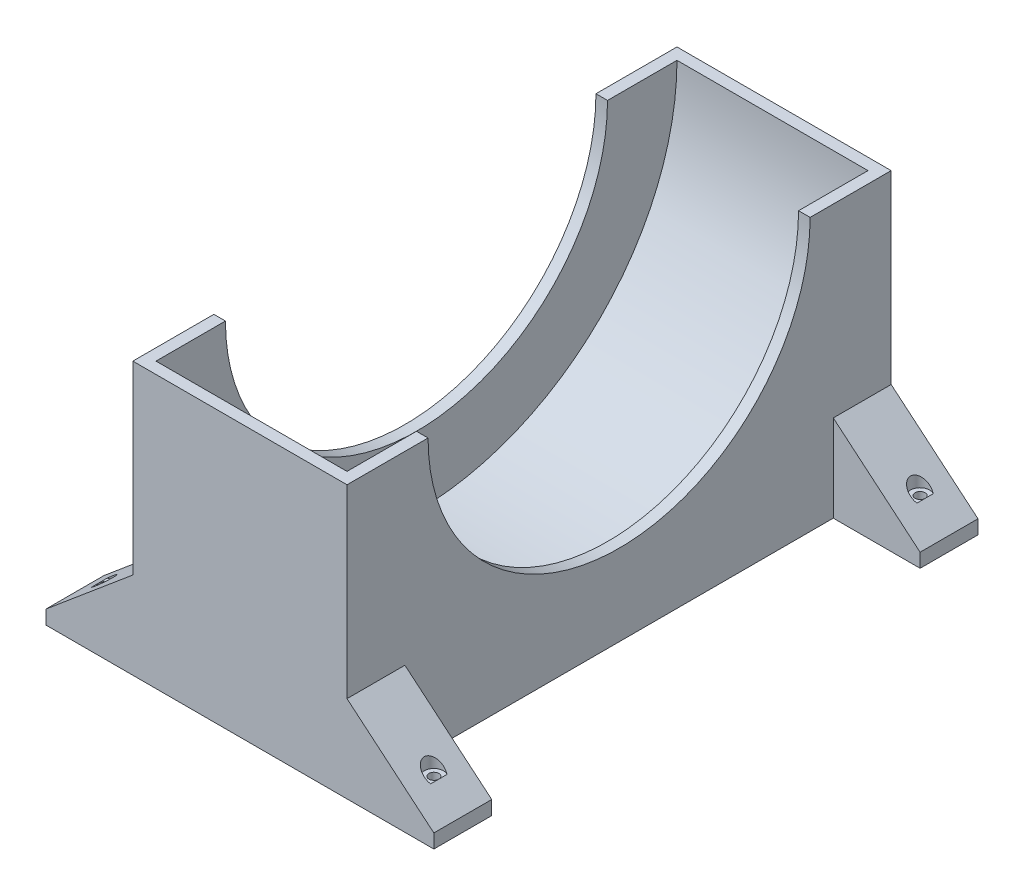
SolidWorks part; units mm, degrees
ref_plane "Front Plane" through (0, 0, 0) normal (0, 0, 1) x (1, 0, 0)
ref_plane "Top Plane" through (0, 0, 0) normal (0, 1, 0) x (1, 0, 0)
ref_plane "Right Plane" through (0, 0, 0) normal (1, 0, 0) x (0, 0, -1)
sketch "Sketch1" plane through (0, 0, 0) normal (1, 0, 0) x (0, 0, -1)
  line L9 (-119.38, 0) -> (-83.82, 0)
  line L10 (83.82, 0) -> (119.38, 0)
  arc A2 (-83.82, 0) -> (83.82, 0) centre (0, 0) ccw
  arc A3 (-119.38, 0) -> (119.38, 0) centre (0, 0) ccw
  dimension "D1" = 83.82
  dimension "D2" = 119.38
extrude "Boss-Extrude1" add sketch "Sketch1" along normal blind 93.98
shell "Shell2" thickness 5.08 removed face at (46.99, 0, -101.6) removed face at (46.99, -41.91, 0) removed face at (46.99, 0, 101.6)
sketch "Sketch6" plane through (0, 0, 0) normal (1, 0, 0) x (0, 0, -1)
  line L3 (-119.38, 0) -> (-119.38, -119.38)
  line L4 (-119.38, -119.38) -> (0, -119.38)
  arc A0 (-119.38, 0) -> (0, -119.38) centre (0, 0) ccw
  dimension "D1" = 119.38
extrude "Boss-Extrude2" add sketch "Sketch6" along normal blind 93.98
sketch "Sketch8" plane through (0, 0, 0) normal (0, 1, 0) x (1, 0, 0)
  circle A0 centre (15.875, -132.08) radius 2.1828
  circle A1 centre (78.74, -132.08) radius 2.1828
  dimension "D1" = 4.3656
  dimension "D2" = 4.3656
  dimension "D3" = 78.74
  dimension "D4" = 15.875
  dimension "D5" = 132.08
sketch "Sketch9" plane through (0, 0, 119.38) normal (0, 0, 1) x (1, 0, 0)
  line L1 (0, -119.38) -> (31.75, -119.38)
  line L2 (0, -119.38) -> (0, -106.68)
  line L3 (0, -106.68) -> (31.75, -106.68)
  line L4 (31.75, -119.38) -> (31.75, -106.68)
  line L5 (93.98, -119.38) -> (62.23, -119.38)
  line L6 (93.98, -119.38) -> (93.98, -106.68)
  line L7 (93.98, -106.68) -> (62.23, -106.68)
  line L8 (62.23, -119.38) -> (62.23, -106.68)
  dimension "D1" = 12.7
  dimension "D2" = 31.75
  dimension "D3" = 12.7
extrude "Boss-Extrude3" add sketch "Sketch9" along normal blind 25.4
extrude "Cut-Extrude2" cut sketch "Sketch8" against normal through all
mirror "Mirror2" about plane through (0, 0, 0) normal (0, 0, 1) of "Boss-Extrude2", "Boss-Extrude3", "Cut-Extrude2"
sketch "Sketch10" plane through (0, 0, 0) normal (-1, 0, 0) x (0, 0, 1)
  line L1 (-119.38, -119.38) -> (-93.98, -119.38)
  line L2 (-119.38, -119.38) -> (-119.38, -81.28)
  line L3 (-119.38, -81.28) -> (-93.98, -81.28)
  line L4 (-93.98, -119.38) -> (-93.98, -81.28)
  line L5 (119.38, -119.38) -> (93.98, -119.38)
  line L6 (119.38, -119.38) -> (119.38, -81.28)
  line L7 (119.38, -81.28) -> (93.98, -81.28)
  line L8 (93.98, -119.38) -> (93.98, -81.28)
  dimension "D1" = 25.4
  dimension "D2" = 38.1
  dimension "D3" = 38.1
  dimension "D4" = 25.4
extrude "Boss-Extrude4" add sketch "Sketch10" along normal blind 38.1
chamfer "Chamfer1" distance 38.1 angle 40 2 edges at (-38.1, -81.28, 106.68) (-38.1, -81.28, -106.68) first distance on face at (-19.05, -81.28, 106.68) first distance on face at (-19.05, -81.28, -106.68)
ref_plane "Plane1" through (46.99, 0, 0) normal (1, 0, 0) x (0, 0, -1)
mirror "Mirror3" about plane through (46.99, 0, 0) normal (1, 0, 0) of "Boss-Extrude4", "Chamfer1"
ref_plane "Plane2" through (0, -119.38, 0) normal (0, 1, 0) x (1, 0, 0)
sketch "Sketch13" plane through (0, -119.38, 0) normal (0, 1, 0) x (1, 0, 0)
  line L0 (-38.1, -119.38) -> (-38.1, -93.98) construction
  line L1 (-38.1, -106.68) -> (-25.4, -106.68)
  line L2 (46.99, -119.38) -> (46.99, -103.2974) construction
  line L3 (93.98, -119.38) -> (0, -119.38) construction
  line L4 (0, 0) -> (42.8126, 0) construction
  circle A0 centre (-25.4, -106.68) radius 2.1828
  circle A1 centre (119.38, -106.68) radius 2.1828
  circle A2 centre (119.38, 106.68) radius 2.1828
  circle A3 centre (-25.4, 106.68) radius 2.1828
  point P19 (-27.5828, -106.68)
  dimension "D1" = 4.3656
  dimension "D2" = 12.7
extrude "Cut-Extrude4" cut sketch "Sketch13" along normal through all contours A0 | A1 | A3 | A2 | A0 region at (-25.4, -119.38, 108.8011) region at (119.38, -119.38, 106.68) region at (119.38, -119.38, -106.68) region at (-25.4, -119.38, -106.68)
sketch "Sketch14" plane through (0, -119.38, 0) normal (0, 1, 0) x (1, 0, 0)
  circle A0 centre (-25.4, -106.68) radius 4.191
  circle A1 centre (119.38, -106.68) radius 4.191
  circle A2 centre (119.38, 106.68) radius 4.191
  circle A3 centre (-25.4, 106.68) radius 4.191
  dimension "D1" = 8.382
sketch "Sketch15" plane through (0, -119.38, 0) normal (0, 1, 0) x (1, 0, 0)
  line L1 (0, -119.38) -> (93.98, -119.38)
  line L2 (0, -119.38) -> (0, -144.78)
  line L3 (0, -144.78) -> (93.98, -144.78)
  line L4 (93.98, -119.38) -> (93.98, -144.78)
  line L5 (0, 144.78) -> (93.98, 144.78)
  line L6 (0, 144.78) -> (0, 119.38)
  line L7 (0, 119.38) -> (93.98, 119.38)
  line L8 (93.98, 144.78) -> (93.98, 119.38)
extrude "Cut-Extrude5" cut sketch "Sketch15" along normal through all
extrude "Cut-Extrude6" cut sketch "Sketch14" against normal blind 25.4 from offset 40.3553
